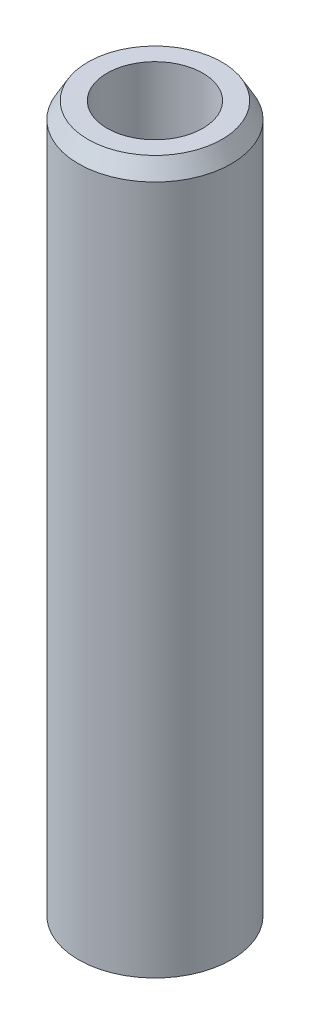
SolidWorks part; units mm, degrees
ref_plane "Front Plane" through (0, 0, 0) normal (0, 0, 1) x (1, 0, 0)
ref_plane "Top Plane" through (0, 0, 0) normal (0, 1, 0) x (1, 0, 0)
ref_plane "Right Plane" through (0, 0, 0) normal (1, 0, 0) x (0, 0, -1)
sketch "Sketch1" plane through (0, 0, 0) normal (0, 1, 0) x (1, 0, 0)
  circle A0 centre (0, 0) radius 7.5
  dimension "SHAFT_OD" = 15
extrude "Boss-Extrude1" add sketch "Sketch1" along normal blind 70.1268
sketch "Sketch2" plane through (0, 0, 0) normal (0, 1, 0) x (1, 0, 0)
  circle A0 centre (0, 0) radius 4.6922
  dimension "BORE_D" = 9.3844
extrude "Cut-Extrude1" cut sketch "Sketch2" along normal through all
chamfer "Chamfer1" distance 1.6077 angle 30 2 edges at (0, 70.1268, 7.5) (0, 0, 7.5) first distance on face at (0, 70.1268, 7.5) first distance on face at (0, 0, 4.6922)
